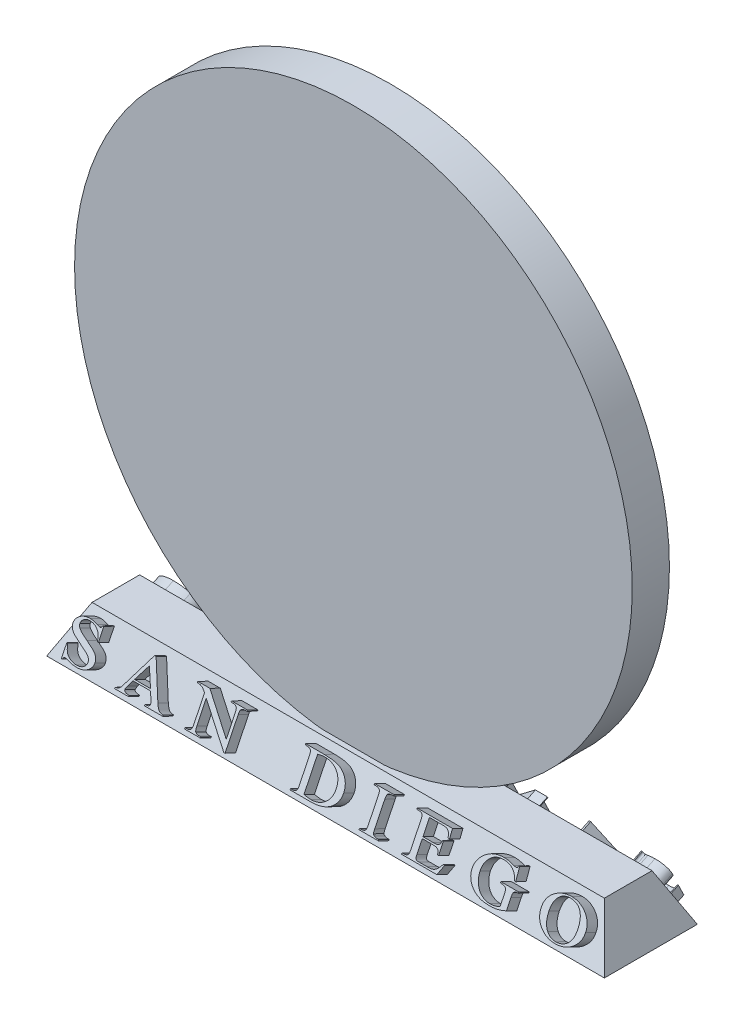
SolidWorks part; units mm, degrees
ref_plane "Front Plane" through (0, 0, 0) normal (0, 0, 1) x (1, 0, 0)
ref_plane "Top Plane" through (0, 0, 0) normal (0, 1, 0) x (1, 0, 0)
ref_plane "Right Plane" through (0, 0, 0) normal (1, 0, 0) x (0, 0, -1)
sketch "Sketch1" plane through (0, 0, 0) normal (0, 1, 0) x (1, 0, 0)
  line L1 (38.1, 6.35) -> (-38.1, 6.35)
  line L2 (38.1, 6.35) -> (38.1, -6.35)
  line L3 (38.1, -6.35) -> (-38.1, -6.35)
  line L4 (-38.1, 6.35) -> (-38.1, -6.35)
  line L5 (38.1, 6.35) -> (-38.1, -6.35) construction
  line L6 (38.1, -6.35) -> (-38.1, 6.35) construction
  point P0 (0, 0)
extrude "Boss-Extrude1" add sketch "Sketch1" along normal blind 6.35 draft 26
sketch "Sketch2" plane through (0, 0, 0) normal (0, 0, 1) x (1, 0, 0)
  circle A0 centre (0, 44.196) radius 38.1
extrude "Boss-Extrude2" add sketch "Sketch2" along normal blind 2.54 and the other way blind 2.54 separate body
sketch "Sketch3" plane through (0, 2.5019, -5.1297) normal (0, 0.4384, -0.8988) x (-1, 0, 0)
  text T0 "SAN DIEGO" font "Times New Roman" height in points 20
extrude "Boss-Extrude5" add sketch "Sketch3" along normal blind 1.5875 from surface starting at face at (0, 3.175, -4.8014)
sketch "Sketch6" plane through (0, 2.5019, 5.1297) normal (0, 0.4384, 0.8988) x (1, 0, 0)
  text T0 "SAN DIEGO" font "Times New Roman" height in points 20
extrude "Boss-Extrude7" add sketch "Sketch6" along normal blind 1.5875
